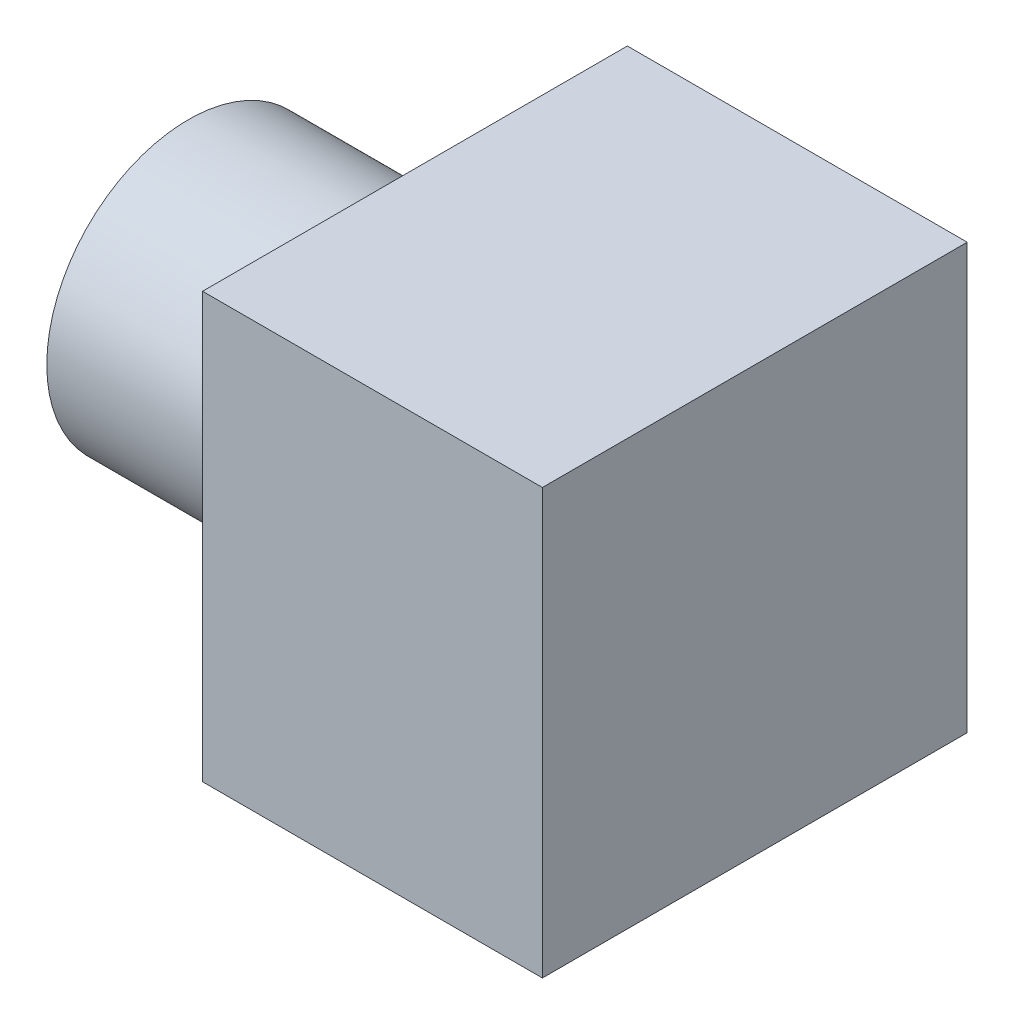
SolidWorks part; units mm, degrees
ref_plane "Front Plane" through (0, 0, 0) normal (0, 0, 1) x (1, 0, 0)
ref_plane "Top Plane" through (0, 0, 0) normal (0, 1, 0) x (1, 0, 0)
ref_plane "Right Plane" through (0, 0, 0) normal (1, 0, 0) x (0, 0, -1)
sketch "Sketch2" plane through (-36.1378, 0, 0) normal (-1, 0, 0) x (0, 0, 1)
  circle A0 centre (-25, -31.6006) radius 5
extrude "Boss-Extrude1" add sketch "Sketch2" along normal blind 8
sketch "Sketch3" plane through (-36.1378, 0, 0) normal (1, 0, 0) x (0, 0, -1)
  line L1 (17.5, -24.1006) -> (32.5, -24.1006)
  line L2 (17.5, -24.1006) -> (17.5, -39.1006)
  line L3 (17.5, -39.1006) -> (32.5, -39.1006)
  line L4 (32.5, -24.1006) -> (32.5, -39.1006)
  circle A0 centre (25, -31.6006) radius 5 construction
  dimension "D1" = 7.5
  dimension "D2" = 15
  dimension "D3" = 7.5
  dimension "D4" = 15
extrude "Boss-Extrude2" add sketch "Sketch3" along normal blind 12
